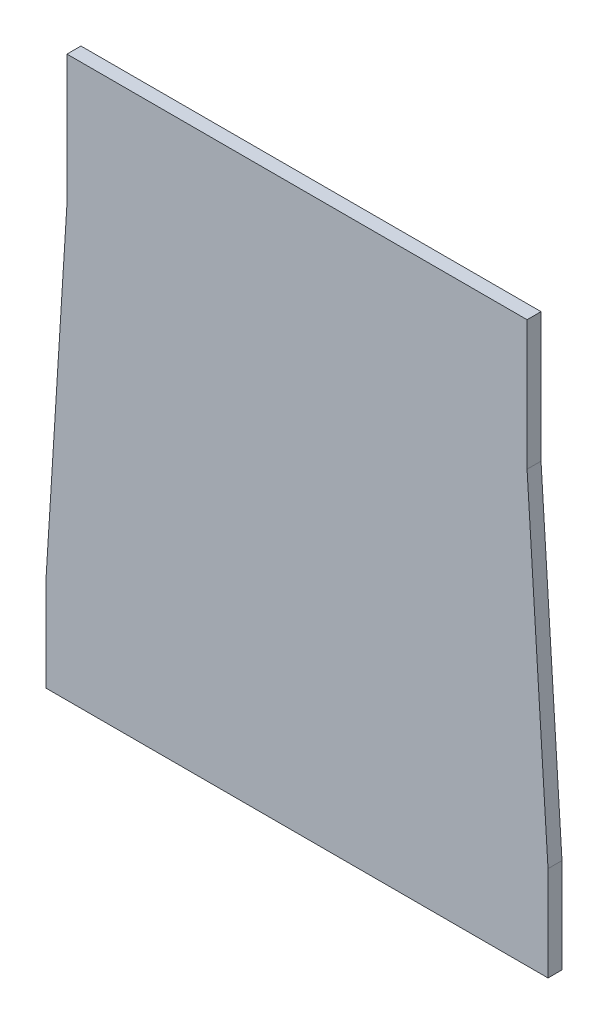
SolidWorks part; units mm, degrees
material "MDF"
ref_plane "Front Plane" through (0, 0, 0) normal (0, 0, 1) x (1, 0, 0)
ref_plane "Top Plane" through (0, 0, 0) normal (0, 1, 0) x (1, 0, 0)
ref_plane "Right Plane" through (0, 0, 0) normal (1, 0, 0) x (0, 0, -1)
sketch "Sketch1" plane through (0, 0, 0) normal (0, 0, 1) x (1, 0, 0)
  line L0 (0, -4273.1683) -> (0, -5592.0408) construction
  line L1 (209.0395, -5469.1795) -> (-209.0395, -5469.1795)
  line L2 (209.0395, -5469.1795) -> (209.0395, -5053.2545)
  line L3 (209.0395, -5053.2545) -> (-209.0395, -5053.2545)
  line L4 (0, -5469.1795) -> (0, -5053.2545) construction
  line L5 (-209.0395, -5469.1795) -> (-209.0395, -5053.2545)
  dimension "D1" = 209.0395
  dimension "D2" = 120.65
  dimension "D3" = 415.925
extrude "Boss-Extrude1" add sketch "Sketch1" along normal blind 12.7
sketch "Sketch2" plane through (0, 0, 0) normal (0, 0, -1) x (-1, 0, 0)
  line L1 (-209.0395, -5469.1795) -> (209.0395, -5469.1795)
  line L2 (-209.0395, -5469.1795) -> (-209.0395, -5548.8695)
  line L3 (-209.0395, -5548.8695) -> (209.0395, -5548.8695)
  line L4 (209.0395, -5469.1795) -> (209.0395, -5548.8695)
  line L8 (209.0395, -5053.2545) -> (209.0395, -5469.1795) construction
  point P7 (0, 0)
  point P8 (0, 0)
  dimension "D1" = 79.69
extrude "Boss-Extrude2" add sketch "Sketch2" against normal through all
sketch "Sketch3" plane through (0, 0, 0) normal (0, 0, -1) x (-1, 0, 0)
  line L1 (209.0395, -5024.8784) -> (-209.0395, -5024.8784)
  line L2 (209.0395, -5024.8784) -> (209.0395, -5053.2545)
  line L3 (209.0395, -5053.2545) -> (-209.0395, -5053.2545)
  line L4 (-209.0395, -5024.8784) -> (-209.0395, -5053.2545)
extrude "Boss-Extrude3" add sketch "Sketch3" against normal through all
sketch "Sketch4" plane through (0, 0, 0) normal (0, 0, -1) x (-1, 0, 0)
  line L0 (209.0388, -5447.3528) -> (228.0888, -5447.3528)
  line L1 (228.0888, -5447.3528) -> (228.0888, -5548.8695)
  line L2 (-209.0395, -5548.8695) -> (209.0395, -5548.8695) construction
  line L3 (228.0888, -5548.8695) -> (209.0395, -5548.8695)
  line L4 (209.0395, -5548.8695) -> (209.0388, -5447.3528)
  line L5 (0, -5562.8703) -> (0, -5024.8784) construction
  line L6 (209.0395, -5024.8784) -> (-209.0395, -5024.8784) construction
  line L7 (-209.0395, -5548.8695) -> (-209.0388, -5447.3528)
  line L8 (-228.0888, -5548.8695) -> (-209.0395, -5548.8695)
  line L9 (-228.0888, -5447.3528) -> (-228.0888, -5548.8695)
  line L10 (-209.0388, -5447.3528) -> (-228.0888, -5447.3528)
extrude "Boss-Extrude4" add sketch "Sketch4" against normal through all
chamfer "Chamfer1" distance 19.05 distance2 304.8 2 edges at (-209.0395, -5447.3528, 6.35) (209.0395, -5447.3528, 6.35) first distance on face at (-218.5641, -5447.3528, 6.35) first distance on face at (218.5641, -5447.3528, 6.35)
sketch "Sketch5" plane through (228.0888, 0, 0) normal (1, 0, 0) x (0, 0, -1)
  line L0 (0, -5447.3417) -> (0, -5548.8695) construction
  line L1 (-12.7, -5548.8695) -> (0, -5548.8695)
  line L2 (-12.7, -5548.8695) -> (-12.7, -5533.4155)
  line L3 (-12.7, -5533.4155) -> (0, -5533.4155)
  line L4 (0, -5548.8695) -> (0, -5533.4155)
  point P7 (-12.7, -5520.6085)
extrude "Cut-Extrude1" cut sketch "Sketch5" against normal through all
